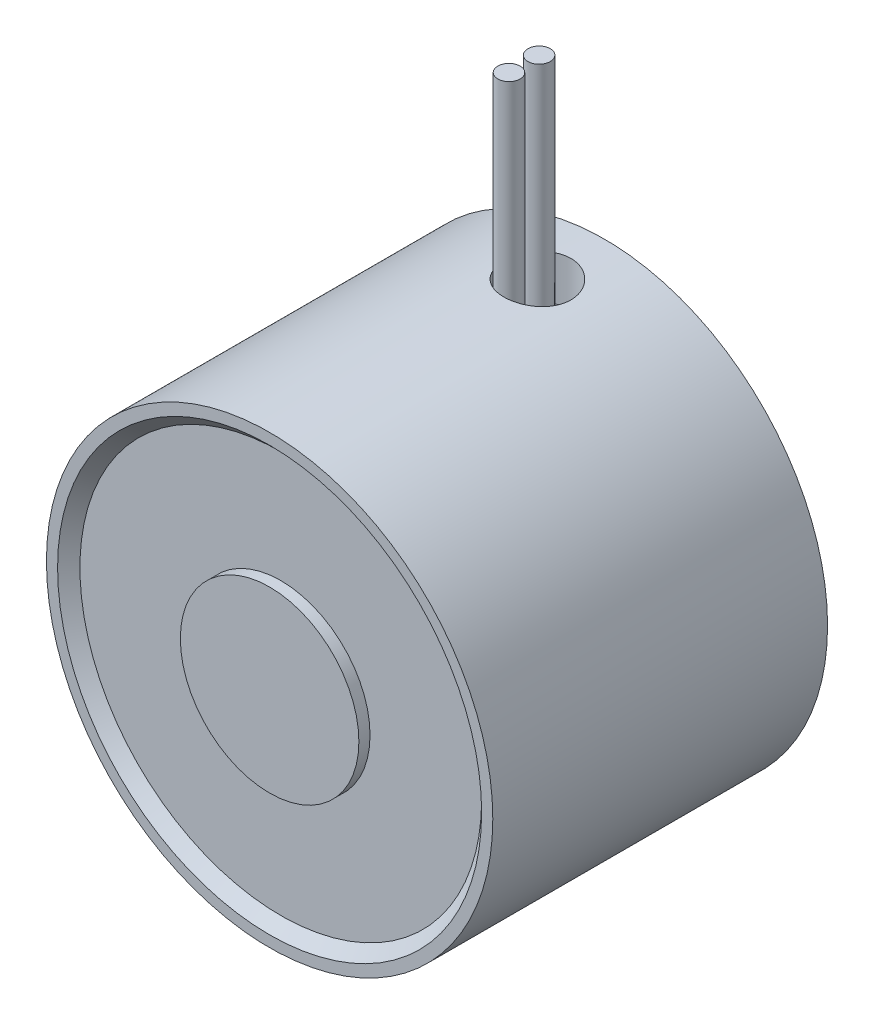
SolidWorks part; units mm, degrees
ref_plane "前视基准面" through (0, 0, 0) normal (0, 0, 1) x (1, 0, 0)
ref_plane "上视基准面" through (0, 0, 0) normal (0, 1, 0) x (1, 0, 0)
ref_plane "右视基准面" through (0, 0, 0) normal (1, 0, 0) x (0, 0, -1)
sketch "草图1" plane through (0, 0, 0) normal (0, 0, 1) x (1, 0, 0)
  circle A0 centre (0, 0) radius 10
  dimension "D1" = 20
extrude "凸台-拉伸1" add sketch "草图1" along normal blind 15
sketch "草图2" plane through (0, 0, 15) normal (0, 0, 1) x (1, 0, 0)
  circle A0 centre (0, 0) radius 4
  circle A1 centre (0, 0) radius 9
  dimension "D1" = 8
  dimension "D2" = 18
extrude "切除-拉伸2" cut sketch "草图2" against normal blind 0.5
chamfer "倒角1" distance 0.5 angle 45 1 edges at (9, 0, 15)
sketch "草图3" plane through (0, 0, 0) normal (0, 0, -1) x (-1, 0, 0)
  circle A0 centre (0, 0) radius 1.5
  dimension "D1" = 3
extrude "切除-拉伸3" cut sketch "草图3" against normal blind 5
chamfer "倒角2" distance 0.5 angle 45 1 edges at (-1.5, 0, 0)
ref_plane "基准面1" through (0, 8, 0) normal (0, 1, 0) x (1, 0, 0)
sketch "草图4" plane through (0, 8, 0) normal (0, 1, 0) x (1, 0, 0)
  circle A0 centre (0, -3) radius 1.5
  dimension "D1" = 3
  dimension "D2" = 3
extrude "切除-拉伸4" cut sketch "草图4" along normal blind 7
sketch "草图5" plane through (0, 8, 0) normal (0, 1, 0) x (1, 0, 0)
  line L0 (-0.6, -1.6252) -> (-0.6, -4.3748) construction
  circle A1 centre (0, -3) radius 1.5 construction
  circle A2 centre (0, -3) radius 1.5 construction
  circle A3 centre (-0.6, -2.3252) radius 0.5
  circle A4 centre (-0.6, -3.6748) radius 0.5
  dimension "D4" = 1
  dimension "D5" = 1
  dimension "D1" = 0.6
  dimension "D2" = 0.7
  dimension "D3" = 0.7
extrude "凸台-拉伸2" add sketch "草图5" along normal blind 10
